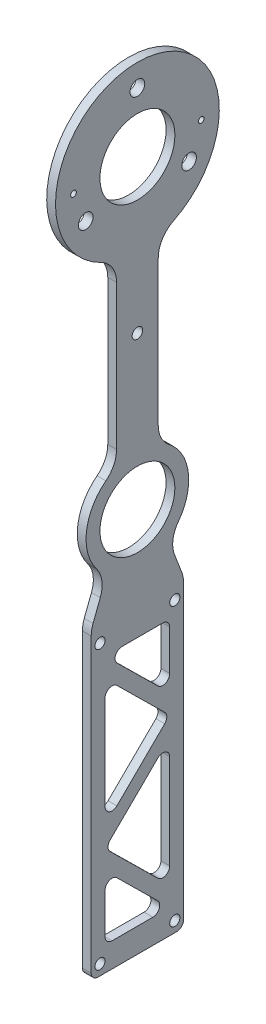
SolidWorks part; units mm, degrees
material "1060 Alloy"
ref_plane "Front Plane" through (0, 0, 0) normal (0, 0, 1) x (1, 0, 0)
ref_plane "Top Plane" through (0, 0, 0) normal (0, 1, 0) x (1, 0, 0)
ref_plane "Right Plane" through (0, 0, 0) normal (1, 0, 0) x (0, 0, -1)
sketch "Sketch1" plane through (0, 0, 0) normal (1, 0, 0) x (0, 0, -1)
  line L0 (-13.4747, 0) -> (13.4747, 0) construction
  line L1 (0, 0) -> (0, 21.5063) construction
  line L2 (-13.4747, 0) -> (-4.8481, 22.4073) construction
  line L3 (0, 35) -> (2.6946, 28.0008) construction
  line L4 (13.4747, 0) -> (-13.4747, 0) construction
  line L5 (20.7574, -5) -> (-20.7574, -5)
  line L6 (-20.7574, -5) -> (-11.0632, 20.1803)
  line L7 (0.1631, 48.4928) -> (6.6746, 31.5795) construction
  line L8 (0, 35) -> (0, 48.4938) construction
  line L9 (0, 35) -> (0, 48.4938) construction
  line L12 (-7.5, 35) -> (-7.5, 46.2175) construction
  line L13 (7.5, 35) -> (7.5, 46.2175) construction
  line L14 (-7.5, 35) -> (-7.5, 29.4356) construction
  line L15 (7.5, 35) -> (7.5, 29.4356) construction
  line L16 (-13.4747, 0) -> (13.4747, 0) construction
  line L17 (-13.4747, 0) -> (-13.4747, -100) construction
  line L18 (13.4747, 0) -> (13.4747, -100) construction
  line L19 (-13.4747, -100) -> (13.4747, -100) construction
  line L20 (-20.7574, -5) -> (20.7574, -5)
  line L21 (-20.7574, -5) -> (-20.7574, -103.81)
  line L22 (20.7574, -5) -> (20.7574, -103.81)
  line L23 (-20.7574, -103.81) -> (20.7574, -103.81)
  line L24 (-11.0632, 20.1803) -> (-9.1691, 25.1001) construction
  line L25 (-7.5, 29.4356) -> (-6.6746, 31.5795) construction
  line L26 (-20.7574, -5) -> (0, 48.9165) construction
  line L27 (9.1691, 25.1001) -> (11.0632, 20.1803) construction
  line L28 (11.0632, 20.1803) -> (20.7574, -5)
  line L29 (0, 48.9165) -> (20.7574, -5) construction
  line L30 (-7.5, 46.2175) -> (-7.5, 51.9047) construction
  line L31 (-7.5, 51.9047) -> (-7.5, 145)
  line L32 (7.5, 46.2175) -> (7.5, 51.9047) construction
  line L33 (7.5, 51.9047) -> (7.5, 145)
  line L34 (-0.1631, 48.4928) -> (0, 48.9165) construction
  line L35 (0, 48.4938) -> (0, 48.9165) construction
  line L36 (0, 48.9165) -> (0, 145) construction
  line L37 (0, 48.4938) -> (0, 48.9165) construction
  line L38 (0, 48.9165) -> (0, 145) construction
  line L39 (0, 48.9165) -> (0.1631, 48.4928) construction
  line L40 (-9.1691, 25.1001) -> (-7.5, 29.4356) construction
  line L41 (-4.8481, 22.4073) -> (-2.6946, 28.0008) construction
  line L42 (-2.6946, 28.0008) -> (0, 35) construction
  line L43 (-13.4747, 0) -> (0, 35) construction
  line L44 (0, 21.5063) -> (0, 27.5) construction
  line L45 (0, 27.5) -> (0, 35) construction
  line L46 (2.6946, 28.0008) -> (4.8481, 22.4073) construction
  line L47 (4.8481, 22.4073) -> (13.4747, 0) construction
  line L48 (0, 35) -> (13.4747, 0) construction
  line L49 (7.5, 29.4356) -> (9.1691, 25.1001) construction
  line L50 (6.6746, 31.5795) -> (7.5, 29.4356) construction
  line L51 (-6.6746, 31.5795) -> (-0.1631, 48.4928) construction
  circle A0 centre (-13.4747, 0) radius 1.8288
  circle A1 centre (0, 35) radius 13.4937
  circle A2 centre (13.4747, 0) radius 1.8288
  circle A3 centre (0, 145) radius 3 construction
  arc A6 (-7.5, 35) -> (-6.6746, 31.5795) centre (0, 35) ccw construction
  arc A7 (7.5, 145) -> (-7.5, 145) centre (0, 145) ccw
  circle A8 centre (-13.4747, -100) radius 1.8288
  circle A9 centre (13.4747, -100) radius 1.8288
  circle A10 centre (0, 145) radius 21.5 construction
  circle A11 centre (0, 166.5) radius 2.65
  circle A12 centre (-18.6195, 134.25) radius 2.65
  circle A13 centre (18.6195, 134.25) radius 2.65
  arc A14 (0, 166.5) -> (-18.6195, 134.25) centre (0, 145) ccw construction
  arc A15 (0, 166.5) -> (18.6195, 134.25) centre (0, 145) cw construction
  arc A16 (-18.6195, 134.25) -> (18.6195, 134.25) centre (0, 145) ccw construction
  circle A17 centre (0, 145) radius 13.5
  circle A18 centre (0, 145) radius 29.5
  arc A19 (11.0632, 20.1803) -> (7.5, 51.9047) centre (0, 35) ccw
  arc A20 (-11.0632, 20.1803) -> (-6.6445, 17.7411) centre (0, 35) ccw construction
  circle A21 centre (0, 35) radius 18.4937 construction
  arc A22 (-6.6445, 17.7411) -> (0, 16.5063) centre (0, 35) ccw construction
  arc A23 (0, 16.5063) -> (6.6445, 17.7411) centre (0, 35) ccw construction
  arc A24 (6.6445, 17.7411) -> (11.0632, 20.1803) centre (0, 35) ccw construction
  arc A25 (0, 53.4937) -> (-7.5, 51.9047) centre (0, 35) ccw construction
  arc A26 (-7.5, 51.9047) -> (-11.0632, 20.1803) centre (0, 35) ccw
  arc A27 (7.5, 51.9047) -> (0, 53.4937) centre (0, 35) ccw construction
  arc A28 (2.6946, 28.0008) -> (6.6746, 31.5795) centre (0, 35) ccw construction
  arc A29 (6.6746, 31.5795) -> (7.5, 35) centre (0, 35) ccw construction
  arc A30 (-2.6946, 28.0008) -> (0, 27.5) centre (0, 35) ccw construction
  arc A31 (0, 27.5) -> (2.6946, 28.0008) centre (0, 35) ccw construction
  arc A32 (-6.6746, 31.5795) -> (-2.6946, 28.0008) centre (0, 35) ccw construction
  point P4 (0, 0)
  point P14 (0, 90)
  point P34 (0, 145)
  dimension "D3" = 3.6576
  dimension "D4" = 26.9875
  dimension "D7" = 6
  dimension "D11" = 43
  dimension "D12" = 5.3
  dimension "D13" = 27
  dimension "D14" = 59
  dimension "D1" = 26.9494
  dimension "D5" = 110
  dimension "D6" = 15
  dimension "D8" = 100
  dimension "D9" = 3.81
  dimension "D10" = 35
  dimension "D15" = 5
  dimension "D2" = 5
extrude "Boss-Extrude1" add sketch "Sketch1" along normal blind 3.175 contours L13 A18 L12 A17 A11 A12 A13 | L12 A18 L13 A17 | A18 L12 A6 L6 L7 L13 | L6 A6 L7 A1 | A6 L6 L5 L7 A2 A0 | A6 L14 L6 | A6 L7 L15 | L21 L23 L22 L5 A9 A8 region at (0, -54.1702, 0) region at (0, -3.7163, 0) region at (0, 124.037, 0) region at (0, 125.1222, -8.3276)
sketch "Sketch2" plane through (3.175, 0, 0) normal (1, 0, 0) x (0, 0, -1)
  line L0 (-11.645, -5) -> (11.645, -5) construction
  line L1 (-11.645, -95) -> (11.645, -95) construction
  line L2 (11.645, -95) -> (11.645, -5) construction
  line L3 (-11.645, -95) -> (-11.645, -5) construction
  line L6 (11.645, -38.5118) -> (-11.645, -61.4882) construction
  line L7 (11.645, -5) -> (-11.645, -5)
  line L8 (-11.645, -5) -> (11.645, -27.9764)
  line L9 (11.645, -27.9764) -> (11.645, -5)
  line L10 (-11.645, -12.0236) -> (11.645, -35)
  line L11 (11.645, -35) -> (-11.645, -57.9764)
  line L12 (-11.645, -57.9764) -> (-11.645, -35)
  line L13 (-11.645, -35) -> (-11.645, -12.0236)
  line L14 (-11.645, -72.0236) -> (-11.645, -95)
  line L15 (-11.645, -95) -> (11.645, -95)
  line L16 (11.645, -95) -> (-11.645, -72.0236)
  line L17 (11.645, -42.0236) -> (11.645, -65)
  line L18 (11.645, -65) -> (11.645, -87.9764)
  line L19 (11.645, -87.9764) -> (-11.645, -65)
  line L20 (-11.645, -65) -> (11.645, -42.0236)
  line L21 (16.645, -1056.0877) -> (16.645, 48943.9123) construction
  line L22 (-16.645, -1060.2922) -> (-16.645, 48939.7078) construction
  line L23 (16.645, 21.5062) -> (-16.645, 21.5062) construction
  line L24 (-20.7574, -103.81) -> (-16.645, -103.81)
  line L25 (-20.7574, -103.81) -> (-20.7574, 21.5062)
  line L26 (-16.645, -103.81) -> (-16.645, 21.5062)
  line L27 (-20.7574, 21.5062) -> (-16.645, 21.5062)
  line L28 (-20.7574, -103.81) -> (20.7574, -103.81) construction
  line L29 (20.7574, -103.81) -> (16.645, -103.81)
  line L30 (20.7574, -103.81) -> (20.7574, 21.5063)
  line L31 (16.645, -103.81) -> (16.645, 21.5062)
  line L32 (20.7574, 21.5063) -> (16.645, 21.5062)
  circle A0 centre (13.4747, 0) radius 1.8288 construction
  circle A1 centre (13.4747, -100) radius 1.8288 construction
  circle A2 centre (0, 35) radius 13.4937 construction
  point P6 (11.645, -50)
  point P10 (0, 21.5063)
  point P21 (0, -50)
  dimension "D1" = 33.29
  dimension "D2" = 5
  dimension "D3" = 5
  dimension "D4" = 5
  dimension "D5" = 5
  dimension "D6" = 2.5
  dimension "D8" = 5
  dimension "D7" = 2
extrude "Cut-Extrude1" cut sketch "Sketch2" against normal up to next
fillet "Fillet3" radius 2.5 14 edges at (1.5875, -57.9764, 11.645) (1.5875, -35, -11.645) (1.5875, -95, -11.645) (1.5875, -72.0236, 11.645) (1.5875, -95, 11.645) (1.5875, -27.9764, -11.645) (1.5875, -5, -11.645) (1.5875, -12.0236, 11.645) (1.5875, -5, 11.645) (1.5875, -87.9764, -11.645) (1.5875, -42.0236, -11.645) (1.5875, -65, 11.645) (1.5875, -103.81, -16.645) (1.5875, -103.81, 16.645)
fillet "Fillet4" radius 10 8 edges at (1.5875, 5.6818, 16.645) (1.5875, 116.4693, 7.5) (1.5875, 116.4693, -7.5) (1.5875, 51.9047, -7.5) (1.5875, 51.9047, 7.5) (1.5875, 20.1803, 11.0632) (1.5875, 20.1803, -11.0632) (1.5875, 5.6818, -16.645)
hole_wizard "M2.5x0.45 Tapped Hole1" positions "Sketch3" profile "Sketch4" tap size "M2.5x0.45" standard "ANSI Metric" end condition up to next
sketch "Sketch3" plane through (3.175, 0, 0) normal (1, 0, 0) x (0, 0, -1)
  line L0 (0, 166.5) -> (0, 145) construction
  line L2 (0, 145) -> (50000, 145) construction
  circle A0 centre (0, 145) radius 23.015 construction
  point P15 (-23.015, 145)
  point P17 (23.015, 145)
  dimension "D1" = 46.03
sketch "Sketch4" plane through (3.175, 145, -23.015) normal (0, 1, 0) x (0, 0, -1)
  line L0 (0, 0) -> (0, 3.175)
  line L1 (0, 3.175) -> (1.025, 3.175)
  line L2 (1.025, 3.175) -> (1.025, 0)
  line L5 (1.025, 0) -> (0, 0)
  line L11 (0, -6.35) -> (0, 107.95) construction
  dimension "Thru Tap Drill Dia." = 2.05
  dimension "Thru Tap Drill Depth" = 3.175
cosmetic thread "Hole Thread1" parameters "D2"=2.5
cosmetic thread "Hole Thread2" parameters "D2"=2.5
hole_wizard "#6 Clearance Hole1" positions "Sketch5" profile "Sketch6" hole size "#6" standard "ANSI Inch"
sketch "Sketch5" plane through (3.175, 0, 0) normal (1, 0, 0) x (0, 0, -1)
  circle A0 centre (0, 35) radius 13.4937 construction
  point P0 (0, 90)
  dimension "D1" = 55
sketch "Sketch6" plane through (3.175, 90, 0) normal (0, 1, 0) x (0, 0, -1)
  line L0 (0, 0) -> (0, 13.9708)
  line L1 (0, 13.9708) -> (1.8986, 12.83)
  line L2 (1.8986, 12.83) -> (1.8986, 0)
  line L5 (1.8986, 0) -> (0, 0)
  line L10 (0, 13.9708) -> (-1.8987, 12.83) construction
  line L11 (0, -6.35) -> (0, 107.95) construction
  dimension "Hole Dia." = 3.7973
  dimension "Hole Depth" = 12.83
  dimension "Drill Angle" = 118
